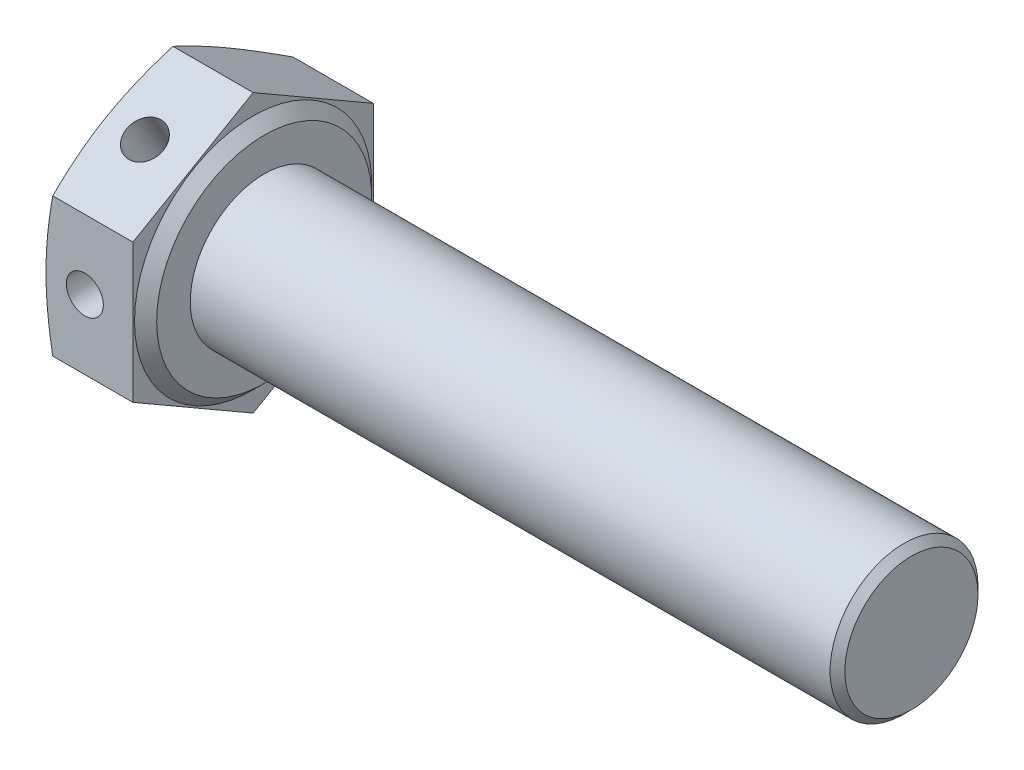
SolidWorks part; units mm, degrees
ref_plane "Front" through (0, 0, 0) normal (0, 0, 1) x (1, 0, 0)
ref_plane "Top" through (0, 0, 0) normal (0, 1, 0) x (1, 0, 0)
ref_plane "Right" through (0, 0, 0) normal (1, 0, 0) x (0, 0, -1)
sketch "Sketch2" plane through (0, 0, 0) normal (1, 0, 0) x (0, 0, -1)
  line L1 (0, -7.5056) -> (6.5, -3.7528)
  line L2 (6.5, -3.7528) -> (6.5, 3.7528)
  line L3 (6.5, 3.7528) -> (0, 7.5056)
  line L4 (0, 7.5056) -> (-6.5, 3.7528)
  line L5 (-6.5, 3.7528) -> (-6.5, -3.7528)
  line L6 (-6.5, -3.7528) -> (0, -7.5056)
  circle A0 centre (0, 0) radius 6.5 construction
extrude "BaseHead" add sketch "Sketch2" along normal blind 5.3
sketch "Sketch3" plane through (0, 0, 0) normal (0, 0, 1) x (1, 0, 0)
  line L0 (5.3, 7.5056) -> (5.3, 5.815)
  line L2 (5.3, 5.815) -> (4.7, 6.415)
  line L3 (4.7, 6.415) -> (4.7, 7.5056)
  line L5 (4.7, 7.5056) -> (5.3, 7.5056)
  line L6 (-0.9571, 0) -> (7.6478, 0) construction
  line L7 (5.3, 7.5056) -> (0, 7.5056) construction
  dimension "D1" = 45
  dimension "c" = 0.6
  dimension "dw" = 11.63
revolve "BearingFace" cut sketch "Sketch3" angle 360 about L6
sketch "Sketch4" plane through (0, 0, 0) normal (0, 0, 1) x (1, 0, 0)
  line L0 (-0.4935, 0) -> (3.5626, 0) construction
  line L2 (0, 7.5056) -> (0.366, 7.5056)
  line L4 (0.366, 7.5056) -> (0, 6.5)
  line L6 (0, 6.5) -> (0, 7.5056)
  line L7 (4.7, 7.5056) -> (0, 7.5056) construction
  dimension "D1" = 20
  dimension "D2" = 13
revolve "HeadChamfer" cut sketch "Sketch4" angle 360 about L0
ref_plane "Plane1" through (23.3, 0, 0) normal (1, 0, 0) x (0, 0, -1)
sketch "Sketch5" plane through (5.3, 0, 0) normal (1, 0, 0) x (0, 0, -1)
  circle A0 centre (0, 0) radius 4
extrude "BaseBody" add sketch "Sketch5" along normal blind 35
cosmetic thread "ThreadCosmetic1" [suppressed] parameters "b"=17, "D2"=7
chamfer "Chamfer1" distance 0.4 angle 45 1 edges at (40.3, 0, -4)
sketch "Sketch6" plane through (0, 0, 0) normal (0, 0, 1) x (1, 0, 0)
  line L2 (4.7, 3.7528) -> (4.7, -3.7528) construction
  line L3 (39.9, 0) -> (5.3, 0) construction
  circle A0 centre (2.1, 0) radius 1
  dimension "d1" = 2
  dimension "h" = 2.6
extrude "Hole" cut sketch "Sketch6" against normal through all and the other way through all
pattern_circular "CirPattern1" count 2 over 60 about axis through (40.3, 0, 0) along (-1, 0, 0) of "Hole"
fillet "HeadFillet" [suppressed] radius 0.4
sketch "Sketch7" plane through (0, 0, 0) normal (0, 0, 1) x (1, 0, 0)
  line L0 (39.359, 4.2) -> (39.899, 4.2)
  line L1 (39.899, 4.2) -> (39.899, 4)
  line L2 (39.899, 4) -> (39.629, 3.5323)
  line L3 (39.359, 4) -> (39.629, 3.5323)
  line L4 (39.359, 4.2) -> (39.359, 4)
  line L5 (41.2163, 0) -> (0, 0) construction
  line L6 (39.359, 4) -> (39.899, 4) construction
  line L7 (39.629, 4) -> (39.629, 3.5323) construction
  line L8 (39.9, 4) -> (5.3, 4) construction
  point P5 (39.629, 4.2)
  dimension "D1" = 0.2
  dimension "D2" = 0.54
  dimension "D3" = 0.001
revolve "Cut-Revolve10" [suppressed] cut sketch "Sketch7" angle 360 about L5
pattern_linear "LPattern10" [suppressed] count 26 spacing 0.648 of bodies 107
equation "\"D2@Sketch4\" = \"s@Sketch2\""
equation "\"b@ThreadCosmetic1\" = \"l@BaseBody\" - \"lg@Plane1\""
equation "\"D1@Chamfer1\" = 0.05 * \"d@Sketch5\""
equation "\"D3@LPattern10\" = \"D2@Sketch7\" * 1.2"
equation "\"D1@LPattern10\" = \"b@ThreadCosmetic1\" / \"D3@LPattern10\""
